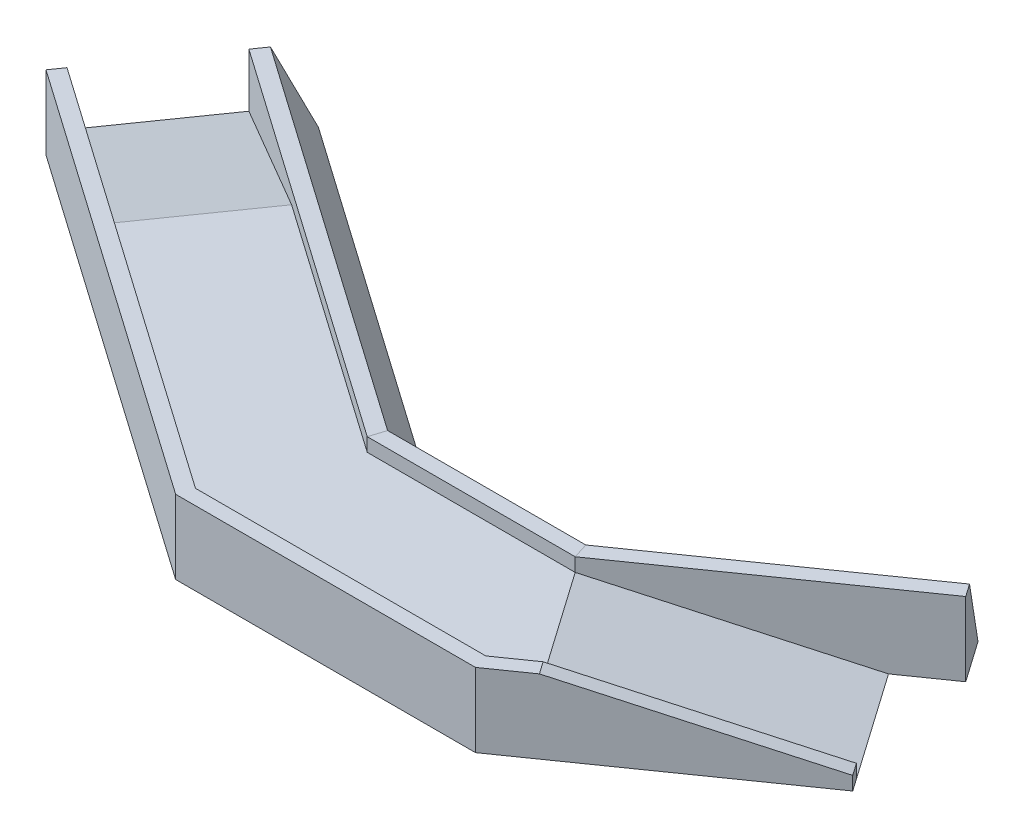
SolidWorks part; units mm, degrees
ref_plane "前视基准面" through (0, 0, 0) normal (0, 0, 1) x (1, 0, 0)
ref_plane "上视基准面" through (0, 0, 0) normal (0, 1, 0) x (1, 0, 0)
ref_plane "右视基准面" through (0, 0, 0) normal (1, 0, 0) x (0, 0, -1)
sketch "草图1" plane through (0, 0, 0) normal (0, 1, 0) x (1, 0, 0)
  line L0 (3904.3046, 1284.2376) -> (4649.9539, 219.34)
  line L1 (4649.9539, 219.34) -> (2480.1116, -1300)
  line L2 (2480.1116, -1300) -> (-409.8884, -1300)
  line L3 (-409.8884, -1300) -> (-4675.2131, 1686.6125)
  line L4 (-4675.2131, 1686.6125) -> (-3929.5638, 2751.5102)
  line L5 (-3929.5638, 2751.5102) -> (0, 0)
  line L6 (0, 0) -> (2070.2231, 0)
  line L7 (2070.2231, 0) -> (3904.3046, 1284.2376)
  line L8 (2070.2231, 0) -> (2815.8725, -1064.8977)
  dimension "D1" = 145
  dimension "D2" = 145
  dimension "D3" = 2239
  dimension "D4" = 1300
  dimension "D5" = 2890
  dimension "D6" = 5207
  dimension "D7" = 1300
  dimension "D8" = 1300
extrude "凸台-拉伸1" add sketch "草图1" along normal blind 600 contours L8 L6 L5 L4 L3 L2 L1 | L7 L8 L1 L0 region at (3360.0885, 0, -109.67) region at (-1069.6198, 0, -262.9645)
sketch "草图2" plane through (0, 600, 0) normal (0, 1, 0) x (1, 0, 0)
  line L0 (4649.9539, 219.34) -> (4735.9904, 96.4672)
  line L1 (4735.9904, 96.4672) -> (2527.4064, -1450)
  line L2 (2527.4064, -1450) -> (-457.1832, -1450)
  line L3 (-457.1832, -1450) -> (-4761.2496, 1563.7397)
  line L4 (-4761.2496, 1563.7397) -> (-4675.2131, 1686.6125)
  line L5 (-409.8884, -1300) -> (-4675.2131, 1686.6125) construction
  line L6 (2480.1116, -1300) -> (-409.8884, -1300) construction
  line L7 (4649.9539, 219.34) -> (2480.1116, -1300) construction
  line L8 (3904.3046, 1284.2376) -> (4649.9539, 219.34) construction
  line L9 (-4675.2131, 1686.6125) -> (-3929.5638, 2751.5102) construction
  line L10 (-4675.2131, 1686.6125) -> (-409.8884, -1300)
  line L11 (-409.8884, -1300) -> (2480.1116, -1300)
  line L12 (2480.1116, -1300) -> (4649.9539, 219.34)
  dimension "D1" = 150
  dimension "D2" = 150
  dimension "D3" = 150
extrude "凸台-拉伸2" add sketch "草图2" against normal up to surface (600 mm away) and the other way blind 135 up to face at (511.241, 0, -417.7125)
sketch "草图3" plane through (-3929.5638, 0, -2751.5102) normal (-0.8192, 0, -0.5736) x (-0.5736, 0, 0.8192)
  line L0 (0, 0) -> (0, 735)
  line L1 (2310.8306, 0) -> (-2310.8306, 0) construction
  line L2 (0, 600) -> (0, 0) construction
  line L3 (0, 735) -> (-154.2639, 735)
  line L4 (-154.2639, 735) -> (-497, 0)
  line L5 (-497, 0) -> (0, 0)
  line L10 (1450, 735) -> (1450, 0) construction
  dimension "D1" = 115
  dimension "D2" = 1947
  dimension "D3" = 735
sketch "草图4" plane through (0, 600, 0) normal (0, 1, 0) x (1, 0, 0)
  line L0 (-3929.5638, 2751.5102) -> (0, 0)
  line L1 (0, 0) -> (2070.2231, 0)
  line L2 (2070.2231, 0) -> (4356.4765, 1600.8518)
  line L3 (3904.3046, 1284.2376) -> (4649.9539, 219.34) construction
  line L4 (2070.2231, 0) -> (3904.3046, 1284.2376) construction
  dimension "D1" = 552
sweep "扫描1" add profiles "草图3" path "草图4"
sketch "草图5" plane through (681.0826, 0, 972.6867) normal (0.5736, 0, 0.8192) x (0.8192, 0, -0.5736)
  line L0 (3934.8275, 0) -> (1695.597, 600)
  line L4 (3934.8275, 600) -> (3934.8275, 0)
  line L5 (2310.8306, 0) -> (-2310.8306, 0) construction
  line L7 (3934.8275, 735) -> (3934.8275, 0) construction
  line L8 (3934.8275, 600) -> (1695.597, 600)
  line L9 (3934.8275, 600) -> (3934.8275, 0) construction
  dimension "D1" = 15
  dimension "D2" = 600
extrude "切除-拉伸1" cut sketch "草图5" along normal up to surface (1300 mm away) up to face at (3565.0328, 667.5, 540.33)
sketch "草图7" plane through (1426.7319, 0, 2037.5844) normal (-0.5736, 0, -0.8192) x (-0.8192, 0, 0.5736)
  line L0 (-1695.597, 600) -> (-1695.597, 735)
  line L1 (-3934.8275, 735) -> (-1285.9391, 735) construction
  line L2 (-1695.597, 735) -> (-3934.8275, 135)
  line L3 (-3934.8275, 735) -> (-3934.8275, 0) construction
  line L4 (-3934.8275, 135) -> (-3934.8275, 735)
  line L5 (-3934.8275, 735) -> (-1695.597, 735)
  line L6 (-1695.597, 600) -> (-3934.8275, 0) construction
  line M4 (-3934.8275, 735) -> (-3934.8275, 0)
  line M8 (-1285.9391, 735) -> (-3934.8275, 735)
extrude "切除-拉伸2" cut sketch "草图7" against normal through all contours L2 M8 M4 region at (4038.5305, 535, 208.7833)
sketch "草图8" plane through (-745.6494, 0, 1064.8977) normal (0.5736, 0, -0.8192) x (-0.8192, 0, -0.5736)
  line L0 (4797.1116, 200) -> (2479.772, 735)
  line L1 (2479.772, 735) -> (4797.1116, 735)
  line L2 (4797.1116, 735) -> (4797.1116, 200)
  line L3 (4797.1116, 0) -> (156.7035, 0) construction
  dimension "D1" = 200
  dimension "D2" = 13
extrude "切除-拉伸3" cut sketch "草图8" along normal up to surface (1300 mm away) up to face at (-1964.7819, 667.5, -1375.7551)
